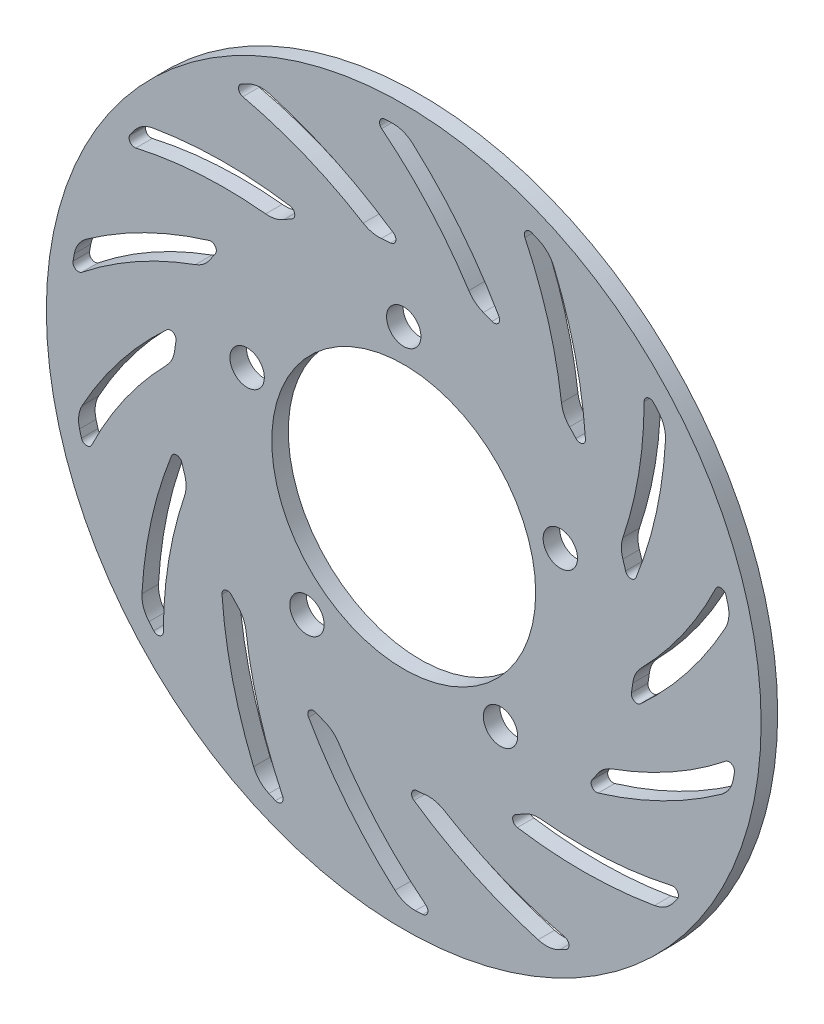
SolidWorks part; units mm, degrees
material "Plain Carbon Steel"
ref_plane "Front" through (0, 0, 0) normal (0, 0, 1) x (1, 0, 0)
ref_plane "Top" through (0, 0, 0) normal (0, 1, 0) x (1, 0, 0)
ref_plane "Right" through (0, 0, 0) normal (1, 0, 0) x (0, 0, -1)
sketch "Sketch1" plane through (0, 0, 0) normal (0, 0, 1) x (1, 0, 0)
  circle A0 centre (0, 0) radius 103.1875
  dimension "D1" = 206.375
base flange "Base-Flange1" sketch "Sketch1" thickness 4.7752 reverse thickness direction no parameters "D1"=5.9436
sketch "Sketch6" plane through (0, 0, 0) normal (0, 0, 1) x (1, 0, 0)
  line L0 (0, 47.5344) -> (45.2079, 14.6889) construction
  line L1 (45.2079, 14.6889) -> (27.94, -38.4561) construction
  line L2 (27.94, -38.4561) -> (-27.94, -38.4561) construction
  line L3 (-27.94, -38.4561) -> (-45.2079, 14.6889) construction
  line L4 (-45.2079, 14.6889) -> (0, 47.5344) construction
  line L5 (0, 47.5344) -> (0, 0) construction
  line L6 (0, 0) -> (45.2079, 14.6889) construction
  line L7 (-45.2079, 14.6889) -> (0, 0) construction
  line L8 (0, 0) -> (-27.94, -38.4561) construction
  line L9 (27.94, -38.4561) -> (0, 0) construction
  circle A0 centre (0, 47.5344) radius 4.9609
  circle A1 centre (45.2079, 14.6889) radius 4.9609
  circle A2 centre (27.94, -38.4561) radius 4.9609
  circle A3 centre (-27.94, -38.4561) radius 4.9609
  circle A4 centre (-45.2079, 14.6889) radius 4.9609
  dimension "D9" = 9.9219
  dimension "D1" = 108
  dimension "D2" = 54
  dimension "D3" = 54
  dimension "D4" = 108
  dimension "D5" = 54
  dimension "D6" = 108
  dimension "D7" = 54
  dimension "D8" = 108
  dimension "D10" = 55.88
extrude "Cut-Extrude1" cut sketch "Sketch6" against normal through all normal cut yes
sketch "Sketch7" plane through (0, 0, 0) normal (0, 0, 1) x (1, 0, 0)
  circle A0 centre (0, 0) radius 38.1
  dimension "D1" = 76.2
extrude "Cut-Extrude2" cut sketch "Sketch7" against normal through all normal cut yes
sketch "Sketch8" plane through (0, 0, 0) normal (0, 0, 1) x (1, 0, 0)
  line L1 (-2.3813, 100.0125) -> (2.3813, 100.0125)
  line L2 (-2.3813, 100.0125) -> (-2.3812, 90.4875)
  line L3 (-2.3812, 90.4875) -> (2.3812, 90.4875)
  line L4 (2.3813, 100.0125) -> (2.3812, 90.4875)
  circle A2 centre (0, 0) radius 103.1875 construction
  point P4 (0, 90.4875)
  dimension "D1" = 3.175
  dimension "D2" = 4.7625
  dimension "D3" = 9.525
extrude "Cut-Extrude3" [suppressed] cut sketch "Sketch8" against normal through all
fillet "Fillet1" [suppressed] radius 2.3813
pattern_circular "CirPattern1" [suppressed] count 10 over 360
sketch "Sketch9" [suppressed] plane through (0, 0, 0) normal (0, 0, 1) x (1, 0, 0)
  line L0 (-23.5585, 99.991) -> (-23.5585, 68.1043) construction
  line L1 (-22.8681, 66.7946) -> (-15.8614, 61.9955) construction
  line L2 (15.8614, 61.9955) -> (22.8681, 66.7946) construction
  line L3 (23.5585, 68.1043) -> (23.5585, 99.991) construction
  arc A0 (-22.2023, 101.5616) -> (22.2023, 101.5616) centre (0, -49.2125) cw construction
  arc A1 (-14.81, 61.7252) -> (14.81, 61.7252) centre (0, -89.9535) cw construction
  arc A2 (-22.2023, 101.5616) -> (-23.5585, 99.991) centre (-21.971, 99.991) ccw construction
  arc A3 (-22.8681, 66.7946) -> (-23.5585, 68.1043) centre (-21.971, 68.1043) cw construction
  arc A4 (-15.8614, 61.9955) -> (-14.81, 61.7252) centre (-14.9643, 63.3052) ccw construction
  arc A5 (15.8614, 61.9955) -> (14.81, 61.7252) centre (14.9643, 63.3052) cw construction
  arc A6 (22.8681, 66.7946) -> (23.5585, 68.1043) centre (21.971, 68.1043) ccw construction
  arc A7 (23.5585, 99.991) -> (22.2023, 101.5616) centre (21.971, 99.991) ccw construction
  circle A10 centre (0, 0) radius 103.1875 construction
  point P22 (0, 103.1875)
  dimension "D1" = 152.4
  dimension "D2" = 152.4
  dimension "D3" = 1.5875
sketch "Sketch10" plane through (0, 0, 0) normal (0, 0, 1) x (1, 0, 0)
  line L0 (0, 0) -> (0, 115.5021) construction
  line L1 (-6.2459, 63.1921) -> (-9.525, 96.3679)
  line L2 (6.2459, 63.1921) -> (9.525, 96.3679)
  circle A5 centre (0, 0) radius 96.8375
  arc A6 (9.525, 96.3679) -> (-9.525, 96.3679) centre (0, 0) ccw
  circle A8 centre (0, 0) radius 63.5
  arc A9 (6.2459, 63.1921) -> (-6.2459, 63.1921) centre (0, 0) ccw
  dimension "D3" = 9.525
  dimension "D1" = 6.35
  dimension "D2" = 25.4
extrude "Cut-Extrude4" [suppressed] cut sketch "Sketch10" against normal through all and the other way through all
sketch "Sketch11" plane through (0, 0, 0) normal (0, 0, 1) x (1, 0, 0)
  line L0 (0, 95.25) -> (0, 63.5) construction
  line L1 (4.7625, 95.25) -> (4.7625, 63.5)
  line L2 (-4.7625, 95.25) -> (-4.7625, 63.5)
  arc A0 (4.7625, 95.25) -> (-4.7625, 95.25) centre (0, 95.25) ccw
  arc A1 (-4.7625, 63.5) -> (4.7625, 63.5) centre (0, 63.5) ccw
  circle A4 centre (0, 0) radius 103.1875 construction
  point P3 (0, 79.375)
  dimension "D1" = 9.525
  dimension "D2" = 95.25
  dimension "D3" = 63.5
extrude "Cut-Extrude5" [suppressed] cut sketch "Sketch11" against normal through all
pattern_circular "CirPattern2" [suppressed] count 10 over 360
sketch "Sketch14" plane through (0, 0, 0) normal (0, 0, 1) x (1, 0, 0)
  arc A0 (0, 96.8375) -> (29.767, 59.6614) centre (-78.9127, 3.1466) cw
  arc A1 (-9.6207, 96.3584) -> (20.3187, 63.5036) centre (-78.9127, 3.1466) cw
  circle A2 centre (0, 0) radius 96.8375
  arc A3 (0, 96.8375) -> (-9.6207, 96.3584) centre (0, 0) ccw
  circle A5 centre (0, 0) radius 66.675
  arc A6 (29.767, 59.6614) -> (20.3187, 63.5036) centre (0, 0) ccw
  dimension "D3" = 6.35
  dimension "D4" = 44.45
  dimension "D5" = 47.625
  dimension "D1" = 6.35
  dimension "D2" = 28.575
extrude "Cut-Extrude6" cut sketch "Sketch14" against normal through all normal cut yes
fillet "Fillet2" radius 1.5875 2 edges at (-9.6207, 96.3584, -2.3876) (29.767, 59.6614, -2.3876)
fillet "Fillet3" radius 8.4667 2 edges at (20.3187, 63.5036, -2.3876) (0, 96.8375, -2.3876)
pattern_circular "CirPattern3" count 14 over 360 about axis through (0, 0, 0) along (0, 0, 1) of "Fillet2", "Cut-Extrude6", "Fillet3"
sketch "Bend-Lines1" [suppressed] plane through (0, 0, 0) normal (0, 1, 0) x (1, 0, 0)
sketch "Bounding-Box1" [suppressed] plane through (0, 0, 0) normal (0, 1, 0) x (1, 0, 0)
sheet metal parameters "Sheet-Metal28" thickness 4.7752 parameters "D1"=5.9436
flat pattern "Flat-Pattern28" [suppressed]
sketch "Bend-Lines2" plane through (0, 0, 0) normal (0, 1, 0) x (1, 0, 0)
sketch3d "Bounding-Box2" [suppressed]
  line L0 (103.0719, -103.3028, 0) -> (-103.3029, -103.0719, 0) construction
  line L1 (103.3029, 103.0719, 0) -> (-103.0719, 103.3029, 0) construction
  line L2 (103.0719, -103.3028, 0) -> (103.3029, 103.0719, 0) construction
  line L3 (-103.3029, -103.0719, 0) -> (-103.0719, 103.3029, 0) construction
sheet metal parameters "Sheet-Metal29" thickness 4.7752 parameters "D1"=5.9436
flat pattern "Flat-Pattern28"
sketch "Bend-Lines2" plane through (0, 0, 0) normal (0, 1, 0) x (1, 0, 0)
sketch3d "Bounding-Box2" [suppressed]
  line L0 (-103.0719, -103.3028, 0) -> (103.3029, -103.0719, 0) construction
  line L1 (-103.3029, 103.0719, 0) -> (103.0719, 103.3029, 0) construction
  line L2 (-103.0719, -103.3028, 0) -> (-103.3029, 103.0719, 0) construction
  line L3 (103.3029, -103.0719, 0) -> (103.0719, 103.3029, 0) construction
sheet metal parameters "Sheet-Metal30" thickness 4.7752 parameters "D1"=5.9436
flat pattern "Flat-Pattern28"
sketch "Bend-Lines2" plane through (0, 0, 0) normal (0, 1, 0) x (1, 0, 0)
sketch3d "Bounding-Box2" [suppressed]
  line L0 (-103.0719, -103.3028, 0) -> (103.3029, -103.0719, 0) construction
  line L1 (-103.3029, 103.0719, 0) -> (103.0719, 103.3029, 0) construction
  line L2 (-103.0719, -103.3028, 0) -> (-103.3029, 103.0719, 0) construction
  line L3 (103.3029, -103.0719, 0) -> (103.0719, 103.3029, 0) construction
sheet metal parameters "Sheet-Metal31" thickness 4.7752 parameters "D1"=5.9436
flat pattern "Flat-Pattern28"
sketch "Bend-Lines2" plane through (0, 0, 0) normal (0, 1, 0) x (1, 0, 0)
sketch3d "Bounding-Box2" [suppressed]
  line L0 (-103.0719, -103.3028, 0) -> (103.3029, -103.0719, 0) construction
  line L1 (-103.3029, 103.0719, 0) -> (103.0719, 103.3029, 0) construction
  line L2 (-103.0719, -103.3028, 0) -> (-103.3029, 103.0719, 0) construction
  line L3 (103.3029, -103.0719, 0) -> (103.0719, 103.3029, 0) construction
sheet metal parameters "Sheet-Metal32" thickness 4.7752 parameters "D1"=5.9436
flat pattern "Flat-Pattern28"
sketch "Bend-Lines2" plane through (0, 0, 0) normal (0, 1, 0) x (1, 0, 0)
sketch3d "Bounding-Box2" [suppressed]
  line L0 (-103.0719, -103.3028, 0) -> (103.3029, -103.0719, 0) construction
  line L1 (-103.3029, 103.0719, 0) -> (103.0719, 103.3029, 0) construction
  line L2 (-103.0719, -103.3028, 0) -> (-103.3029, 103.0719, 0) construction
  line L3 (103.3029, -103.0719, 0) -> (103.0719, 103.3029, 0) construction
sheet metal parameters "Sheet-Metal33" thickness 4.7752 parameters "D1"=5.9436
flat pattern "Flat-Pattern28"
sketch "Bend-Lines2" plane through (0, 0, 0) normal (0, 1, 0) x (1, 0, 0)
sketch3d "Bounding-Box2" [suppressed]
  line L0 (-103.0719, -103.3028, 0) -> (103.3029, -103.0719, 0) construction
  line L1 (-103.3029, 103.0719, 0) -> (103.0719, 103.3029, 0) construction
  line L2 (-103.0719, -103.3028, 0) -> (-103.3029, 103.0719, 0) construction
  line L3 (103.3029, -103.0719, 0) -> (103.0719, 103.3029, 0) construction
sheet metal parameters "Sheet-Metal34" thickness 4.7752 parameters "D1"=5.9436
flat pattern "Flat-Pattern28"
sketch "Bend-Lines2" plane through (0, 0, 0) normal (0, 1, 0) x (1, 0, 0)
sketch3d "Bounding-Box2" [suppressed]
  line L0 (-103.0719, -103.3028, 0) -> (103.3029, -103.0719, 0) construction
  line L1 (-103.3029, 103.0719, 0) -> (103.0719, 103.3029, 0) construction
  line L2 (-103.0719, -103.3028, 0) -> (-103.3029, 103.0719, 0) construction
  line L3 (103.3029, -103.0719, 0) -> (103.0719, 103.3029, 0) construction
sheet metal parameters "Sheet-Metal35" thickness 4.7752 parameters "D1"=5.9436
flat pattern "Flat-Pattern28" [suppressed]
sketch "Bend-Lines2" plane through (0, 0, 0) normal (0, 1, 0) x (1, 0, 0)
sketch3d "Bounding-Box2" [suppressed]
  line L0 (103.0719, -103.3028, 0) -> (-103.3029, -103.0719, 0) construction
  line L1 (103.3029, 103.0719, 0) -> (-103.0719, 103.3029, 0) construction
  line L2 (103.0719, -103.3028, 0) -> (103.3029, 103.0719, 0) construction
  line L3 (-103.3029, -103.0719, 0) -> (-103.0719, 103.3029, 0) construction
sketch "Sketch9-1" [suppressed] plane through (0, 0, 0) normal (0, 0, 1) x (1, 0, 0)
  line L0 (-23.5585, 99.991) -> (-23.5585, 68.1043) construction
  line L1 (-22.8681, 66.7946) -> (-15.8614, 61.9955) construction
  line L2 (15.8614, 61.9955) -> (22.8681, 66.7946) construction
  line L3 (23.5585, 68.1043) -> (23.5585, 99.991) construction
  arc A0 (-22.2023, 101.5616) -> (22.2023, 101.5616) centre (0, -49.2125) cw construction
  arc A1 (-14.81, 61.7252) -> (14.81, 61.7252) centre (0, -89.9535) cw construction
  arc A2 (-22.2023, 101.5616) -> (-23.5585, 99.991) centre (-21.971, 99.991) ccw construction
  arc A3 (-22.8681, 66.7946) -> (-23.5585, 68.1043) centre (-21.971, 68.1043) cw construction
  arc A4 (-15.8614, 61.9955) -> (-14.81, 61.7252) centre (-14.9643, 63.3052) ccw construction
  arc A5 (15.8614, 61.9955) -> (14.81, 61.7252) centre (14.9643, 63.3052) cw construction
  arc A6 (22.8681, 66.7946) -> (23.5585, 68.1043) centre (21.971, 68.1043) ccw construction
  arc A7 (23.5585, 99.991) -> (22.2023, 101.5616) centre (21.971, 99.991) ccw construction
  dimension "D1" = 152.4
  dimension "D2" = 152.4
  dimension "D3" = 1.5875
sketch "Sketch9-2" [suppressed] plane through (0, 0, 0) normal (0, 0, 1) x (1, 0, 0)
  line L0 (-23.5585, 99.991) -> (-23.5585, 68.1043) construction
  line L1 (-22.8681, 66.7946) -> (-15.8614, 61.9955) construction
  line L2 (15.8614, 61.9955) -> (22.8681, 66.7946) construction
  line L3 (23.5585, 68.1043) -> (23.5585, 99.991) construction
  arc A0 (-22.2023, 101.5616) -> (22.2023, 101.5616) centre (0, -49.2125) cw construction
  arc A1 (-14.81, 61.7252) -> (14.81, 61.7252) centre (0, -89.9535) cw construction
  arc A2 (-22.2023, 101.5616) -> (-23.5585, 99.991) centre (-21.971, 99.991) ccw construction
  arc A3 (-22.8681, 66.7946) -> (-23.5585, 68.1043) centre (-21.971, 68.1043) cw construction
  arc A4 (-15.8614, 61.9955) -> (-14.81, 61.7252) centre (-14.9643, 63.3052) ccw construction
  arc A5 (15.8614, 61.9955) -> (14.81, 61.7252) centre (14.9643, 63.3052) cw construction
  arc A6 (22.8681, 66.7946) -> (23.5585, 68.1043) centre (21.971, 68.1043) ccw construction
  arc A7 (23.5585, 99.991) -> (22.2023, 101.5616) centre (21.971, 99.991) ccw construction
  dimension "D1" = 152.4
  dimension "D2" = 152.4
  dimension "D3" = 1.5875
sheet metal parameters "Sheet-Metal38" thickness 4.7752 parameters "D1"=5.9436
flat pattern "Flat-Pattern28"
sketch "Bend-Lines2" plane through (0, 0, 0) normal (0, 1, 0) x (1, 0, 0)
sketch3d "Bounding-Box2" [suppressed]
  line L0 (-103.0719, -103.3028, 0) -> (103.3029, -103.0719, 0) construction
  line L1 (-103.3029, 103.0719, 0) -> (103.0719, 103.3029, 0) construction
  line L2 (-103.0719, -103.3028, 0) -> (-103.3029, 103.0719, 0) construction
  line L3 (103.3029, -103.0719, 0) -> (103.0719, 103.3029, 0) construction
sheet metal parameters "Sheet-Metal39" thickness 4.7752 parameters "D1"=5.9436
flat pattern "Flat-Pattern28"
sketch "Bend-Lines2" plane through (0, 0, 0) normal (0, 1, 0) x (1, 0, 0)
sketch3d "Bounding-Box2" [suppressed]
  line L0 (-103.0719, -103.3028, 0) -> (103.3029, -103.0719, 0) construction
  line L1 (-103.3029, 103.0719, 0) -> (103.0719, 103.3029, 0) construction
  line L2 (-103.0719, -103.3028, 0) -> (-103.3029, 103.0719, 0) construction
  line L3 (103.3029, -103.0719, 0) -> (103.0719, 103.3029, 0) construction
equation "\"Total Cutting Length\"= \"Cutting Length-Outer\" + \"Cutting Length-Inner\""
equation "\"Amount in ft^2\"= \"Bounding Box Area-Blank\" / 144"
